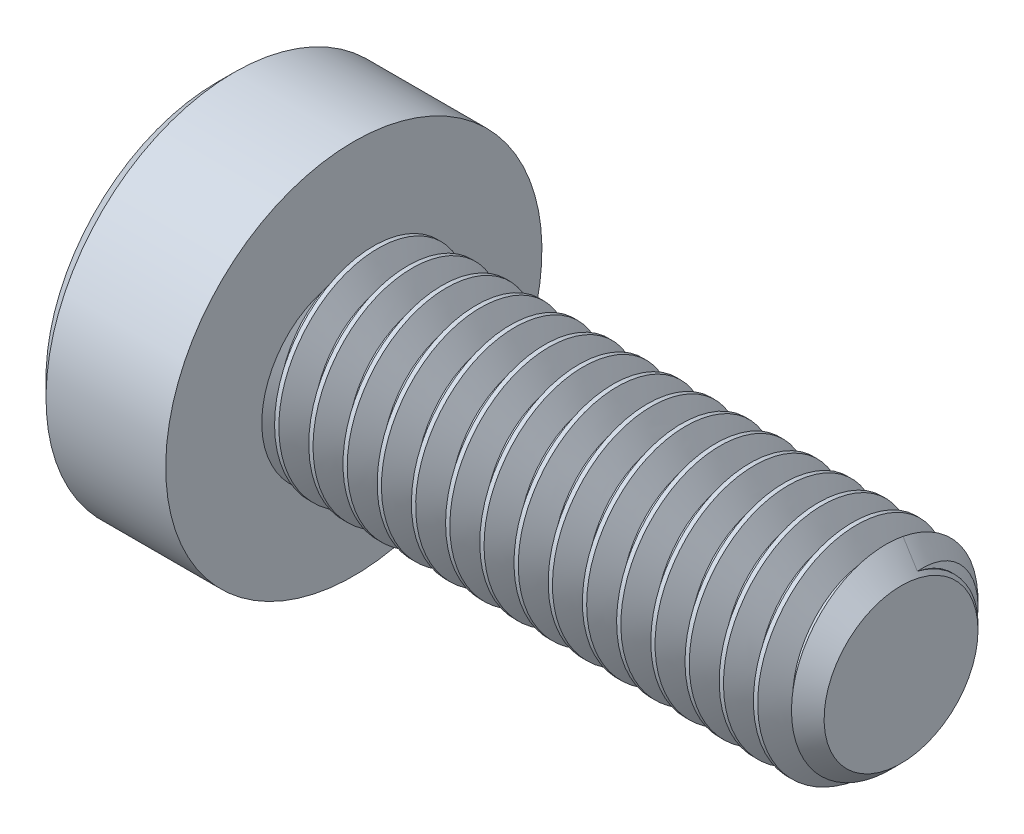
SolidWorks part; units mm, degrees
ref_plane "Front Plane" through (0, 0, 0) normal (0, 0, 1) x (1, 0, 0)
ref_plane "Top Plane" through (0, 0, 0) normal (0, 1, 0) x (1, 0, 0)
ref_plane "Right Plane" through (0, 0, 0) normal (1, 0, 0) x (0, 0, -1)
sketch "Sketch1" plane through (0, 0, 0) normal (0, 0, 1) x (1, 0, 0)
  line L0 (4, 0) -> (-4, 0) construction
  line L1 (4, 1.5) -> (4, -1.5) construction
  line L2 (-4, 2.75) -> (-4, -2.75) construction
  line L3 (-4, 2.75) -> (-5.75, 2.75) construction
  line L4 (-5.75, 2.75) -> (-6, 2.5) construction
  line L5 (-6, 2.5) -> (-6, -2.5) construction
  line L6 (-6, -2.5) -> (-5.75, -2.75) construction
  line L7 (-5.75, -2.75) -> (-4, -2.75) construction
  point P7 (-4.38, 0)
  point P12 (2, -1.5)
  dimension "D1" = 45
  dimension "D2" = 2
  dimension "Dec." = 3
  dimension "Length" = 8
  dimension "Head Dia" = 5.5
  dimension "Head Height" = 2
  dimension "Hex Depth" = 1.62
  dimension "Chamfer" = 0.25
ref_plane "Plane1" through (4, 0, 0) normal (1, 0, 0) x (0, 0, -1)
ref_plane "Plane2" through (-6, 0, 0) normal (1, 0, 0) x (0, 0, -1)
sketch "Sketch2" plane through (4, 0, 0) normal (1, 0, 0) x (0, 0, -1)
  circle A0 centre (0, 0) radius 1.5
extrude "Boss-Extrude1" add sketch "Sketch2" against normal up to vertex (8 mm away) up to point (-4, 0, 0)
sketch "Sketch3" plane through (4, 0, 0) normal (1, 0, 0) x (0, 0, -1)
  circle A0 centre (0, 0) radius 1.5 construction
  circle A1 centre (0, 0) radius 1.5
curve "Helix/Spiral1" pitch 0.5 height 8.5 radius 1.5 centre (4, 0, 0) axis (-1, 0, 0) start towards (0, 1, 0) parameters "Pitch"=0.5
chamfer "Chamfer1" distance 0.375 angle 45 1 edges at (4, 0, -1.5)
sketch "Sketch5" plane through (0, 0, 0) normal (0, 0, 1) x (1, 0, 0)
  line L0 (3.7813, 1.5) -> (4.2188, 1.5)
  line L1 (4.2188, 1.5) -> (4.0313, 1.1752)
  line L2 (4.0313, 1.1752) -> (3.9688, 1.1752)
  line L3 (3.9688, 1.1752) -> (3.7813, 1.5)
  line L4 (4, 1.1752) -> (4, 1.5) construction
  line L5 (3.875, 1.3376) -> (4.125, 1.3376) construction
  dimension "D1" = 60
  dimension "D2" = 0.25
  dimension "D3" = 0.0625
sweep "Cut-Sweep1" cut profiles "Sketch5" path "Helix/Spiral1" align with end faces yes
sketch "Sketch4" plane through (-6, 0, 0) normal (1, 0, 0) x (0, 0, -1)
  line L0 (-2.75, 0.7937) -> (2.75, 0.7937) construction
  line L1 (0, 1.1547) -> (-1, 0.5774)
  line L2 (-1, 0.5774) -> (-1, -0.5774)
  line L3 (-1, -0.5774) -> (0, -1.1547)
  line L4 (0, -1.1547) -> (1, -0.5774)
  line L5 (1, -0.5774) -> (1, 0.5774)
  line L6 (1, 0.5774) -> (0, 1.1547)
  line L7 (0, 0) -> (0, 0.7937) construction
  circle A0 centre (0, 0) radius 1 construction
  dimension "D1" = 5.5
  dimension "Hex Size" = 2
  dimension "D2" = 0.7937
sketch "Sketch6" plane through (0, 0, 0) normal (0, 0, 1) x (1, 0, 0)
  line L0 (-5.75, 2.75) -> (-6, 2.5) construction
  line L1 (-4, 2.75) -> (-5.75, 2.75) construction
  line L2 (-4, 2.75) -> (-4, -2.75) construction
  line L3 (-6, 2.5) -> (-6, -2.5) construction
  line L4 (-5.75, 2.75) -> (-6, 2.5)
  line L5 (-4, 2.75) -> (-5.75, 2.75)
  line L6 (-4, 2.75) -> (-4, 0)
  line L7 (-6, 2.5) -> (-6, 0)
  line L8 (-4, 0) -> (-6, 0) construction
  line L9 (-4, 0) -> (-6, 0)
revolve "Revolve1" add sketch "Sketch6" angle 360 about L8
extrude "Cut-Extrude1" cut sketch "Sketch4" along normal up to vertex (1.62 mm away) up to point (-4.38, 0, 0)
sketch "Sketch8" plane through (-6, 0, 0) normal (-1, 0, 0) x (0, 0, 1)
  circle A1 centre (0, 0) radius 1.1547
extrude "Cut-Extrude2" cut sketch "Sketch8" against normal through all draft 45
equation "\"D3@Helix/Spiral1\" = \"Length@Sketch1\"+\"Pitch@Helix/Spiral1\""
equation "\"D3@Sketch5\" = \"Pitch@Helix/Spiral1\"*.125"
equation "\"D2@Sketch5\" = \"Pitch@Helix/Spiral1\"*.50"
equation "\"D1@Chamfer1\" = \"Pitch@Helix/Spiral1\"*.75"
equation "\"D2@Sketch1\" = \"Pitch@Helix/Spiral1\"*4"
equation "\"D1@Sketch4\" = \"Head Dia@Sketch1\""
equation "\"Chamfer@Sketch1\" = \"Head Height@Sketch1\"/8"
